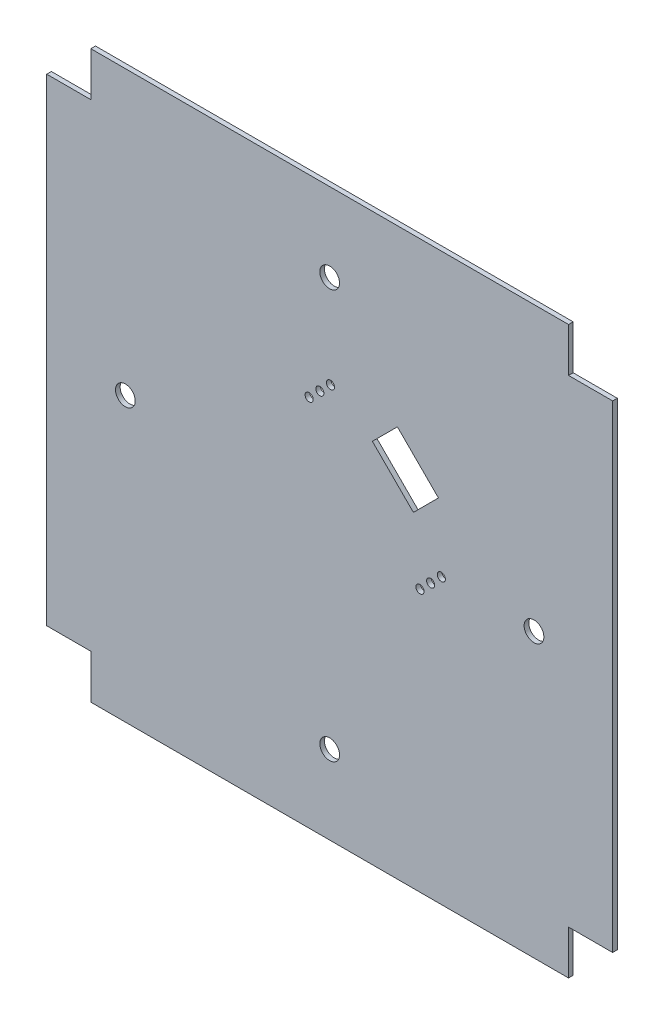
SolidWorks part; units mm, degrees
ref_plane "Front Plane" through (0, 0, 0) normal (0, 0, 1) x (1, 0, 0)
ref_plane "Top Plane" through (0, 0, 0) normal (0, 1, 0) x (1, 0, 0)
ref_plane "Right Plane" through (0, 0, 0) normal (1, 0, 0) x (0, 0, -1)
sketch "Sketch1" plane through (0, 0, 0) normal (0, 0, 1) x (1, 0, 0)
  line L52 (48.75, -48.75) -> (-48.75, -48.75)
  line L53 (48.75, -48.75) -> (48.75, 48.75)
  line L54 (48.75, 48.75) -> (-48.75, 48.75)
  line L55 (-48.75, -48.75) -> (-48.75, 48.75)
  line L56 (48.75, -48.75) -> (-48.75, 48.75) construction
  line L57 (48.75, 48.75) -> (-48.75, -48.75) construction
  point P0 (0, 0)
  dimension "D1" = 97.5
  dimension "D2" = 97.5
extrude "Boss-Extrude1" add sketch "Sketch1" along normal blind 0.8 contours L54 | L53 L52 L55 L54
sketch "Sketch2" plane through (0, 0, 0) normal (0, 0, -1) x (-1, 0, 0)
  line L1 (-48.75, 48.75) -> (-41.15, 48.75)
  line L2 (-48.75, 48.75) -> (-48.75, 41.15)
  line L3 (-48.75, 41.15) -> (-41.15, 41.15)
  line L4 (48.75, 48.75) -> (-48.75, 48.75)
  line L5 (-48.75, 48.75) -> (-48.75, -48.75)
  line L6 (-48.75, -48.75) -> (48.75, -48.75)
  line L7 (48.75, -48.75) -> (48.75, 48.75)
  line L8 (48.75, 48.75) -> (-48.75, 48.75) construction
  line L9 (-48.75, 48.75) -> (-48.75, -48.75) construction
  line L10 (-48.75, -48.75) -> (48.75, -48.75) construction
  line L11 (48.75, -48.75) -> (48.75, 48.75) construction
  line L12 (-41.15, 48.75) -> (-41.15, 41.15)
  line L13 (-48.75, -48.75) -> (-41.15, -48.75)
  line L14 (-48.75, -48.75) -> (-48.75, -41.15)
  line L15 (-48.75, -41.15) -> (-41.15, -41.15)
  line L16 (-41.15, -48.75) -> (-41.15, -41.15)
  line L17 (48.75, -48.75) -> (41.15, -48.75)
  line L18 (48.75, -48.75) -> (48.75, -41.15)
  line L19 (48.75, -41.15) -> (41.15, -41.15)
  line L20 (41.15, -48.75) -> (41.15, -41.15)
  line L21 (48.75, 48.75) -> (41.15, 48.75)
  line L22 (48.75, 48.75) -> (48.75, 41.15)
  line L23 (48.75, 41.15) -> (41.15, 41.15)
  line L24 (41.15, 48.75) -> (41.15, 41.15)
  dimension "D2" = 7.6
  dimension "D3" = 7.6
  dimension "D4" = 7.6
  dimension "D5" = 7.6
  dimension "D6" = 7.6
  dimension "D7" = 7.6
  dimension "D8" = 7.6
  dimension "D9" = 7.6
  dimension "D1" = 0
extrude "Cut-Extrude1" cut sketch "Sketch2" against normal through all
sketch "Sketch3" plane through (0, 0, 0) normal (0, 0, -1) x (-1, 0, 0)
  line L0 (0, 0) -> (0, 48.75) construction
  line L1 (-41.15, 48.75) -> (41.15, 48.75) construction
  line L2 (48.75, 0) -> (0, 0) construction
  line L3 (48.75, -41.15) -> (48.75, 41.15) construction
  line L4 (0, 0) -> (0, -48.75) construction
  line L5 (-41.15, -48.75) -> (41.15, -48.75) construction
  line L6 (0, 0) -> (-48.75, 0) construction
  line L7 (-48.75, -41.15) -> (-48.75, 41.15) construction
  circle A4 centre (0, 35.2) radius 1.7
  circle A5 centre (35.2, 0) radius 1.7
  circle A6 centre (0, -35.2) radius 1.7
  circle A7 centre (-35.2, 0) radius 1.7
  dimension "D5" = 3.4
  dimension "D6" = 3.4
  dimension "D7" = 3.4
  dimension "D8" = 3.4
  dimension "D1" = 35.2
  dimension "D2" = 35.2
  dimension "D3" = 35.2
  dimension "D4" = 35.2
extrude "Cut-Extrude2" cut sketch "Sketch3" against normal through all
sketch "Sketch4" plane through (0, 0, 0) normal (0, 0, -1) x (-1, 0, 0)
  line L5 (-18.7383, 11.6673) -> (-14.425, 7.3539)
  line L6 (-18.7383, 11.6673) -> (-11.6673, 18.7383)
  line L7 (-14.425, 7.3539) -> (-7.3539, 14.425)
  line L8 (-11.6673, 18.7383) -> (-7.3539, 14.425)
  line L9 (-41.15, -48.75) -> (41.15, -48.75) construction
  point P7 (-10.8894, 10.8894)
  point P8 (-132.2984, 65.8162)
  dimension "D1" = 45
  dimension "D2" = 15.4
  dimension "D3" = 6.1
  dimension "D4" = 10
  dimension "D5" = 15.4
extrude "Cut-Extrude3" cut sketch "Sketch4" against normal through all
sketch "Sketch5" plane through (0, 0, 0) normal (0, 0, -1) x (-1, 0, 0)
  line L0 (-7.4573, 26.5492) -> (10.8514, 8.2405) construction
  line L1 (-3.0983, -15.9936) -> (-23.3597, 4.2678) construction
  line L5 (-18.7383, 11.6673) -> (-14.425, 7.3539) construction
  line L7 (-7.3539, 14.425) -> (-11.6673, 18.7383) construction
  line L8 (-14.425, 7.3539) -> (-7.3539, 14.425) construction
  circle A6 centre (-0.1414, 19.2333) radius 0.7
  circle A7 centre (1.6971, 17.3948) radius 0.7
  circle A8 centre (3.5355, 15.5563) radius 0.7
  circle A9 centre (-19.2333, 0.1414) radius 0.7
  circle A10 centre (-17.3948, -1.6971) radius 0.7
  circle A11 centre (-15.5563, -3.5355) radius 0.7
  dimension "D1" = 1.4
  dimension "D2" = 1.4
  dimension "D3" = 1.4
  dimension "D4" = 1.4
  dimension "D5" = 1.4
  dimension "D6" = 1.4
  dimension "D7" = 8.5
  dimension "D8" = 8.5
  dimension "D9" = 2.6
  dimension "D10" = 2.6
  dimension "D11" = 1.7
  dimension "D12" = 1.7
  dimension "D13" = 2.6
  dimension "D14" = 2.6
extrude "Cut-Extrude4" cut sketch "Sketch5" against normal through all
